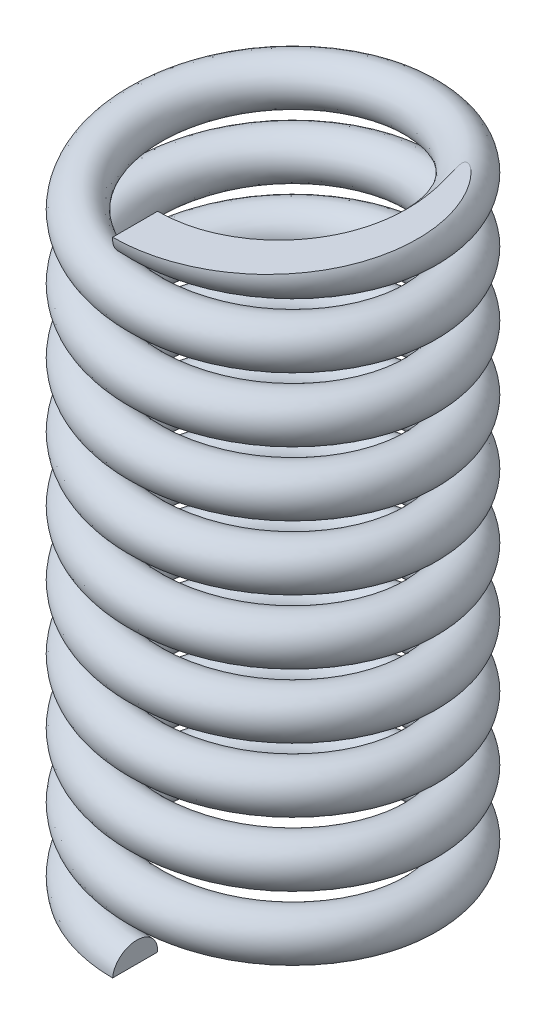
SolidWorks part; units mm, degrees
ref_plane "Front Plane" through (0, 0, 0) normal (0, 0, 1) x (1, 0, 0)
ref_plane "Top Plane" through (0, 0, 0) normal (0, 1, 0) x (1, 0, 0)
ref_plane "Right Plane" through (0, 0, 0) normal (1, 0, 0) x (0, 0, -1)
sketch "Sketch1" plane through (0, 0, 0) normal (0, 1, 0) x (1, 0, 0)
  circle A0 centre (0, 0) radius 2.15
  dimension "D1" = 4.3
curve "Helix/Spiral1" pitch 1 height 10 radius 2.15 left hand yes centre (0, 0, 0) axis (0, 1, 0) start towards (0, 0, 1)
sweep "Sweep2" add path "Helix/Spiral1" circular profile diameter 0.7 parameters "D3"=0.7
sketch "Sketch3" plane through (0, 0, 0) normal (1, 0, 0) x (0, 0, -1)
  line L0 (0, 0) -> (-2.8475, 0)
  line L1 (-2.8475, 0) -> (-2.8475, 10)
  line L2 (-2.8475, 10) -> (0, 10)
  line L3 (0, 10) -> (0, 10.7031)
  line L4 (0, 10.7031) -> (-4.3219, 10.7031)
  line L5 (-4.3219, 10.7031) -> (-4.3219, -0.6056)
  line L6 (-4.3219, -0.6056) -> (0, -0.6056)
  line L7 (0, -0.6056) -> (0, 0)
  dimension "D1" = 10
revolve "Cut-Revolve1" cut sketch "Sketch3" angle 360 about L7
